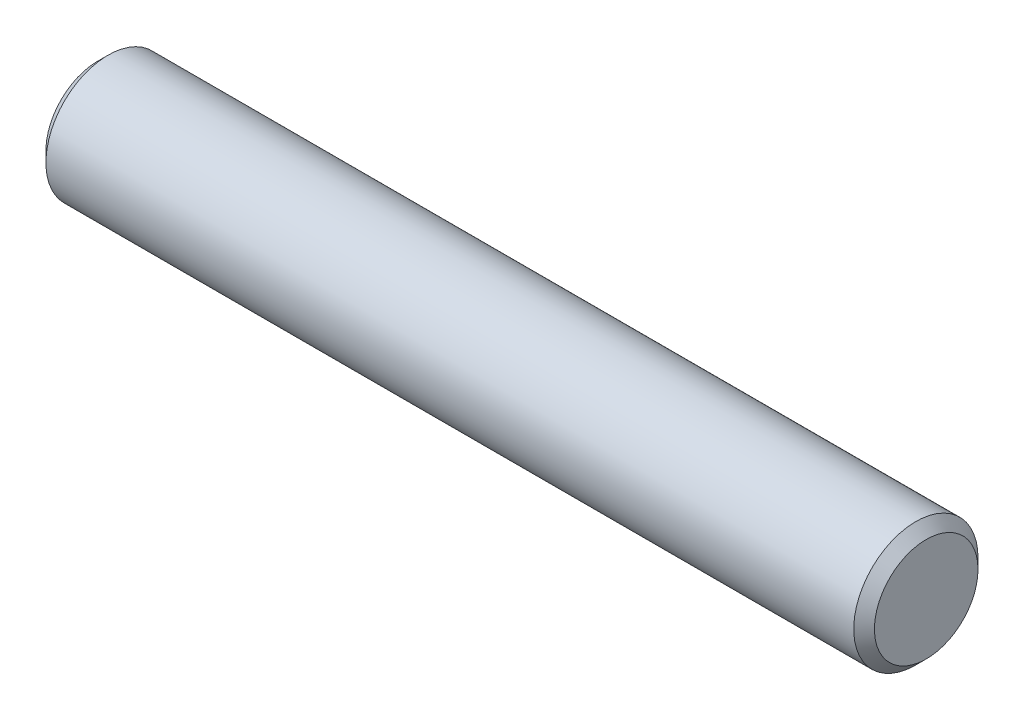
SolidWorks part; units mm, degrees
material "AISI 1020 Сталь, холоднокатаная"
ref_plane "Спереди" through (0, 0, 0) normal (0, 0, 1) x (1, 0, 0)
ref_plane "Сверху" through (0, 0, 0) normal (0, 1, 0) x (1, 0, 0)
ref_plane "Справа" through (0, 0, 0) normal (1, 0, 0) x (0, 0, -1)
sketch "Эскиз1" plane through (0, 0, 0) normal (1, 0, 0) x (0, 0, -1)
  circle A0 centre (0, 0) radius 3
  dimension "D1" = 6
extrude "Бобышка-Вытянуть1" add sketch "Эскиз1" along normal mid plane 40
chamfer "Фаска1" distance 0.5 angle 45 2 edges at (-20, 0, -3) (20, 0, -3)
sketch "Эскиз2" plane through (0, 0, 0) normal (0, 0, 1) x (1, 0, 0)
  line L2 (50, 0) -> (-50, 0) construction
  line L3 (-15, 27.4904) -> (-15, 93.4904) construction
  point P0 (-15, 0)
  point P1 (0, 0)
  point P2 (-20.5728, 5.123)
  point P3 (-16.0298, -4.6474)
  point P4 (-15, -3.0989)
  point P5 (-18.2151, -3.0989)
  point P6 (0, 0)
  point P7 (-15, -1.5652)
  point P8 (0, 0)
  point P9 (-9.6462, -2.1452)
  point P14 (0, 0)
  point P16 (-9.8626, 0)
  point P17 (0, 0)
